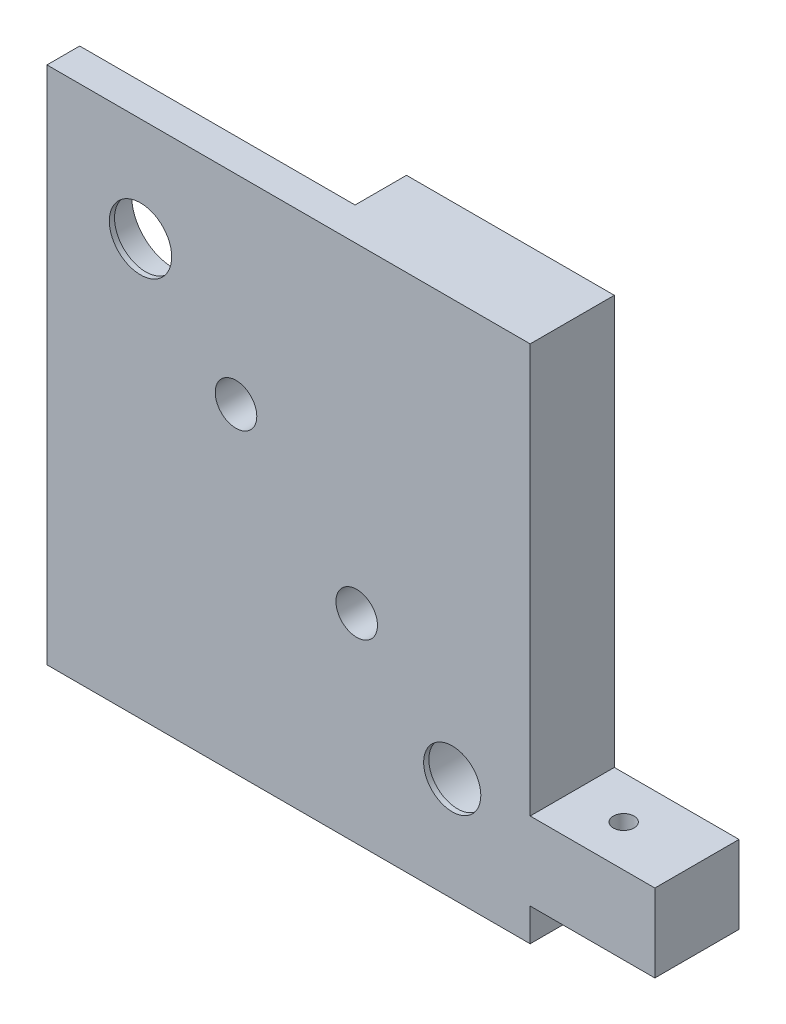
SolidWorks part; units mm, degrees
ref_plane "Front Plane" through (0, 0, 0) normal (0, 0, 1) x (1, 0, 0)
ref_plane "Top Plane" through (0, 0, 0) normal (0, 1, 0) x (1, 0, 0)
ref_plane "Right Plane" through (0, 0, 0) normal (1, 0, 0) x (0, 0, -1)
sketch "Sketch1" plane through (0, 0, 0) normal (0, 0, 1) x (1, 0, 0)
  line L1 (-76.1871, 64.9281) -> (16.8129, 64.9281)
  line L2 (-76.1871, 64.9281) -> (-76.1871, -35.0719)
  line L3 (-76.1871, -35.0719) -> (16.8129, -35.0719)
  line L4 (16.8129, 64.9281) -> (16.8129, -35.0719)
  dimension "D1" = 93
  dimension "D2" = 100
extrude "Boss-Extrude2" add sketch "Sketch1" along normal blind 6.3 contours L1 L4 L3 L2
sketch "Sketch3" plane through (0, 0, 0) normal (0, 0, -1) x (-1, 0, 0)
  line L0 (76.1871, -35.0719) -> (-16.8129, -35.0719) construction
  line L1 (-16.8129, 64.9281) -> (23.1871, 64.9281)
  line L2 (-16.8129, 64.9281) -> (-16.8129, -35.0719)
  line L3 (-16.8129, -35.0719) -> (23.1871, -35.0719)
  line L4 (23.1871, 64.9281) -> (23.1871, -35.0719)
  line L5 (-16.8129, 64.9281) -> (-16.8129, -35.0719) construction
  dimension "D1" = 0
  dimension "D2" = 0
  dimension "D3" = 40
  dimension "D4" = 100
extrude "Boss-Extrude3" add sketch "Sketch3" along normal blind 9.9
sketch "Sketch4" plane through (16.8129, 0, 0) normal (1, 0, 0) x (0, 0, -1)
  line L0 (-6.3, 64.9281) -> (-6.3, -35.0719) construction
  line L1 (-6.3, -13.7719) -> (9.9, -13.7719)
  line L2 (-6.3, -13.7719) -> (-6.3, -28.7719)
  line L3 (-6.3, -28.7719) -> (9.9, -28.7719)
  line L4 (9.9, -13.7719) -> (9.9, -28.7719)
  line L5 (9.9, 64.9281) -> (9.9, -35.0719) construction
  line L6 (-6.3, -35.0719) -> (9.9, -35.0719) construction
  dimension "D1" = 6.3
  dimension "D2" = 15
extrude "Boss-Extrude4" add sketch "Sketch4" along normal blind 24
sketch "Sketch5" plane through (0, -13.7719, 0) normal (0, 1, 0) x (1, 0, 0)
  line L0 (40.8129, -6.3) -> (16.8129, -6.3) construction
  line L2 (16.8129, 9.9) -> (16.8129, -6.3) construction
  circle A0 centre (26.8129, 1.7) radius 2
  dimension "D2" = 4
  dimension "D3" = 10
  dimension "D1" = 8
extrude "Cut-Extrude1" cut sketch "Sketch5" against normal blind 50
sketch "Sketch6" plane through (0, 0, -9.9) normal (0, 0, -1) x (-1, 0, 0)
  line L0 (-16.8129, -35.0719) -> (23.1871, -35.0719) construction
  line L1 (-16.8129, -28.7719) -> (-16.8129, -35.0719) construction
  circle A0 centre (-1.8129, -15.0719) radius 7.5
  dimension "D1" = 15
  dimension "D2" = 20
  dimension "D3" = 15
extrude "Cut-Extrude2" cut sketch "Sketch6" against normal blind 50
sketch "Sketch7" plane through (0, 0, 0) normal (0, 0, -1) x (-1, 0, 0)
  line L0 (76.1871, -35.0719) -> (23.1871, -35.0719) construction
  line L2 (-16.8129, 64.9281) -> (-16.8129, -13.7719) construction
  circle A0 centre (58.1871, 44.9281) radius 8
  dimension "D1" = 16
  dimension "D2" = 80
  dimension "D3" = 75
extrude "Cut-Extrude3" cut sketch "Sketch7" against normal blind 50
extrude "Extrude-Thin1" add sketch "Sketch7<2>" along normal blind 1 from surface thin starting at face at (-50.1871, 44.9281, 6.3) thin type one direction reverse wall 2
sketch "Sketch7<2>" plane through (0, 0, 0) normal (0, 0, -1) x (-1, 0, 0) same geometry as "Sketch7"
extrude "Extrude-Thin2" add sketch "Sketch6<2>" along normal blind 1 from surface thin starting at face at (9.3129, -15.0719, 6.3) thin type one direction reverse wall 2
sketch "Sketch6<2>" plane through (0, 0, -9.9) normal (0, 0, -1) x (-1, 0, 0) same geometry as "Sketch6"
sketch "Sketch8" plane through (0, 0, 6.3) normal (0, 0, 1) x (1, 0, 0)
  line L0 (-58.1871, 44.9281) -> (1.8129, -15.0719)
  line L1 (-39.8023, 26.5433) -> (-39.8023, 63.6954)
  line L2 (-39.8023, 63.6954) -> (-39.8023, 26.5433)
  line L4 (1.8129, -15.0719) -> (1.8129, 44.9281)
  line L5 (1.8129, 44.9281) -> (-58.1871, 44.9281)
  line L6 (-39.8023, 26.5433) -> (-16.5718, 3.3128)
  circle A0 centre (-39.8023, 26.5433) radius 4
  circle A1 centre (-16.5718, 3.3128) radius 4
  circle A2 centre (-39.8023, 26.5433) radius 15.8626
  circle A3 centre (-16.5718, 3.3128) radius 15.8626
  circle A5 centre (-58.1871, 44.9281) radius 12
  circle A9 centre (1.8129, -15.0719) radius 12
  point P6 (-28.1871, 14.9281)
  point P10 (-16.0521, 2.7931)
  point P14 (0, 0)
  point P15 (-14.9802, 1.7212)
  point P16 (-16.4644, 3.2054)
  point P18 (-39.8959, 26.6369)
  point P20 (-39.2213, 25.9623)
  point P21 (0, 0)
  dimension "D1" = 8
  dimension "D2" = 8
  dimension "D3" = 24
  dimension "D4" = 24
  dimension "D5" = 31.7252
  dimension "D6" = 26
  dimension "D7" = 26
extrude "Cut-Extrude4" cut sketch "Sketch8" against normal blind 20 contours L0 A0 L1 | L0 A0 | L1 A0 L0 | L0 A1 | L0 A1 region at (-40.7967, 28.9441, 6.3) region at (-41.0027, 25.3429, 6.3) region at (-37.8702, 27.3436, 6.3) region at (-15.3714, 4.5133, 6.3) region at (-17.7722, 2.1124, 6.3)
